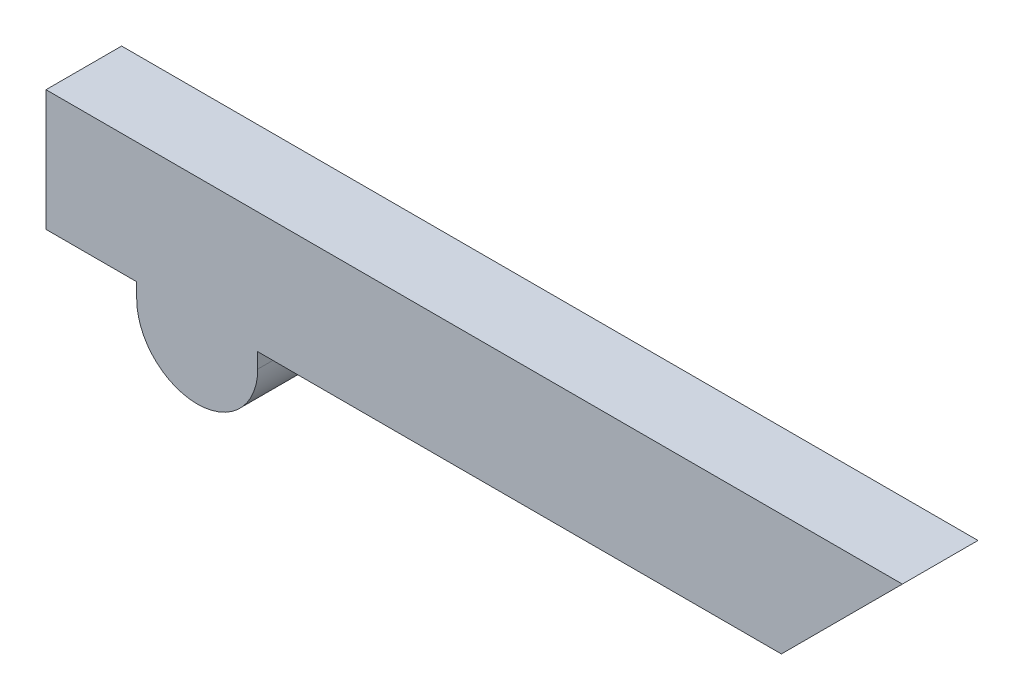
SolidWorks part; units mm, degrees
ref_plane "Front Plane" through (0, 0, 0) normal (0, 0, 1) x (1, 0, 0)
ref_plane "Top Plane" through (0, 0, 0) normal (0, 1, 0) x (1, 0, 0)
ref_plane "Right Plane" through (0, 0, 0) normal (1, 0, 0) x (0, 0, -1)
sketch "Sketch1" plane through (0, 0, 0) normal (0, 0, 1) x (1, 0, 0)
  line L0 (14.4246, 11.475) -> (21.0917, 11.475)
  line L1 (21.0917, 11.475) -> (22.6917, 13.075)
  line L2 (22.6917, 13.075) -> (11.85, 13.075)
  line L3 (11.85, 13.075) -> (11.85, 11.475)
  line L4 (11.85, 11.475) -> (12.8754, 11.475)
  line L5 (11.65, 11.275) -> (12.65, 11.275)
  line L6 (14.65, 11.275) -> (21.1745, 11.275)
  line L7 (21.1745, 11.275) -> (23.1745, 13.275)
  line L8 (23.1745, 13.275) -> (11.65, 13.275)
  line L9 (11.65, 13.275) -> (11.65, 11.275)
  line L10 (11.65, 11.275) -> (12.65, 11.275)
  line L11 (14.65, 11.275) -> (21.1745, 11.275)
  line L12 (21.1745, 11.275) -> (23.1745, 13.275)
  line L13 (23.1745, 13.275) -> (11.65, 13.275)
  line L14 (11.65, 13.275) -> (11.65, 11.275)
  line L15 (11.65, 13.075) -> (22.9745, 13.075)
  line L16 (11.65, 11.475) -> (21.3745, 11.475)
  line L17 (12.85, 11.275) -> (12.85, 11.475)
  line L18 (14.45, 11.275) -> (14.45, 11.475)
  arc A0 (12.8754, 11.475) -> (14.4246, 11.475) centre (13.65, 11.275) ccw
  arc A1 (12.65, 11.275) -> (14.65, 11.275) centre (13.65, 11.275) ccw
  arc A2 (12.65, 11.275) -> (14.65, 11.275) centre (13.65, 11.275) ccw
  dimension "D1" = 0
  dimension "D2" = 0.2
extrude "Shape" add sketch "Sketch1" along normal blind 1 contours L4 L16 L0 L1 L2 L3 | L14 L16 L3 L15 | L1 L16 L12 L15 | L16 A0 | A0 L16 L17 | A0 L18 L0 region at (16.8814, 12.2962, 0) region at (13.65, 11.0406, 0) region at (14.4424, 11.4252, 0) region at (12.8576, 11.4252, 0) region at (22.0331, 12.275, 0) region at (11.75, 12.275, 0)
